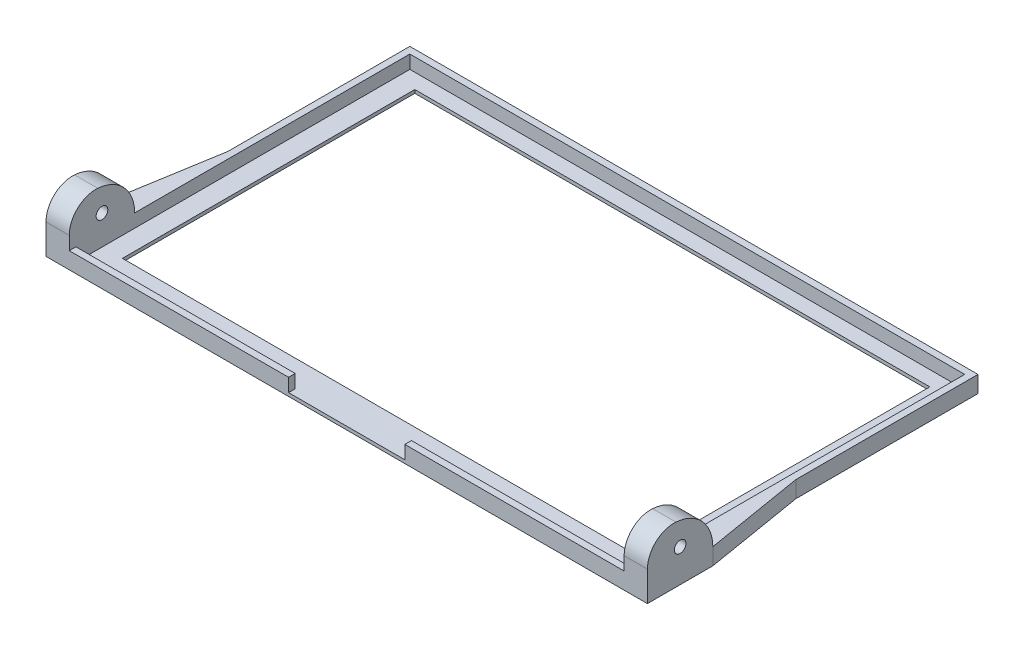
SolidWorks part; units mm, degrees
ref_plane "Front Plane" through (0, 0, 0) normal (0, 0, 1) x (1, 0, 0)
ref_plane "Top Plane" through (0, 0, 0) normal (0, 1, 0) x (1, 0, 0)
ref_plane "Right Plane" through (0, 0, 0) normal (1, 0, 0) x (0, 0, -1)
sketch "Sketch1" plane through (0, 0, 0) normal (0, 1, 0) x (1, 0, 0)
  line L0 (-85.5, 50.5) -> (85.5, 50.5)
  line L1 (-77.5, -44) -> (77.5, -44)
  line L2 (-77.5, -44) -> (-77.5, 44)
  line L3 (-77.5, 44) -> (77.5, 44)
  line L4 (77.5, -44) -> (77.5, 44)
  line L5 (-77.5, -44) -> (77.5, 44) construction
  line L6 (-77.5, 44) -> (77.5, -44) construction
  line L7 (85.5, 50.5) -> (85.5, -54)
  line L8 (85.5, -54) -> (-85.5, -54)
  line L9 (-85.5, -54) -> (-85.5, 50.5)
  point P0 (0, 0)
  dimension "D1" = 155
  dimension "D2" = 88
  dimension "D3" = 8
  dimension "D4" = 8
  dimension "D5" = 6.5
  dimension "D6" = 10
extrude "Boss-Extrude1" add sketch "Sketch1" along normal blind 1
sketch "Sketch2" plane through (0, 1, 0) normal (0, 1, 0) x (1, 0, 0)
  line L0 (-83.5, 48.5) -> (-83.5, -52)
  line L1 (-83.5, -52) -> (83.5, -52)
  line L2 (83.5, -52) -> (83.5, 48.5)
  line L3 (83.5, 48.5) -> (-83.5, 48.5)
  line L4 (-85.5, 50.5) -> (-85.5, -54)
  line L5 (-85.5, -54) -> (85.5, -54)
  line L6 (85.5, -54) -> (85.5, 50.5)
  line L7 (85.5, 50.5) -> (-85.5, 50.5)
  line L8 (-85.5, 50.5) -> (-85.5, -54)
  line L9 (-85.5, -54) -> (85.5, -54)
  line L10 (85.5, -54) -> (85.5, 50.5)
  line L11 (85.5, 50.5) -> (-85.5, 50.5)
  dimension "D1" = 0
  dimension "D2" = 2
extrude "Boss-Extrude2" add sketch "Sketch2" along normal blind 4
sketch "Sketch3" plane through (0, 1, 0) normal (0, 1, 0) x (1, 0, 0)
  line L0 (0, 0) -> (0, -52) construction
  line L1 (-83.5, -52) -> (83.5, -52) construction
  line L3 (-17.5, -56.3497) -> (17.5, -56.3497)
  line L4 (-17.5, -56.3497) -> (-17.5, -47.6503)
  line L5 (-17.5, -47.6503) -> (17.5, -47.6503)
  line L6 (17.5, -56.3497) -> (17.5, -47.6503)
  line L7 (-17.5, -56.3497) -> (17.5, -47.6503) construction
  line L8 (-17.5, -47.6503) -> (17.5, -56.3497) construction
  dimension "D1" = 35
extrude "Cut-Extrude1" cut sketch "Sketch3" along normal blind 14
sketch "Sketch4" plane through (0, 1, 0) normal (0, 1, 0) x (1, 0, 0)
  line L0 (-83.5, 48.5) -> (-83.5, -52) construction
  line L1 (-83.5, -34.3044) -> (-90.5, -34.3044)
  line L2 (-83.5, -34.3044) -> (-83.5, -54)
  line L3 (-83.5, -54) -> (-90.5, -54)
  line L4 (-90.5, -34.3044) -> (-90.5, -54)
  line L5 (-85.5, -54) -> (-17.5, -54) construction
  line L6 (0, 0) -> (0, -54) construction
  line L7 (17.5, -54) -> (-17.5, -54) construction
  line L8 (83.5, -54) -> (90.5, -54)
  line L9 (90.5, -34.3044) -> (90.5, -54)
  line L10 (83.5, -34.3044) -> (90.5, -34.3044)
  line L11 (83.5, -34.3044) -> (83.5, -54)
  dimension "D1" = 7
extrude "Boss-Extrude3" add sketch "Sketch4" along normal blind 16 and the other way blind 1
fillet "Fillet1" radius 12 2 edges at (87, 17, 34.3044) (-87, 17, 34.3044)
chamfer "Chamfer1" distance 5 distance2 30 2 edges at (85.5, 2.5, 34.3044) (-85.5, 2.5, 34.3044) first distance on face at (88, 2.5, 34.3044) first distance on face at (-88, 2.5, 34.3044)
fillet "Fillet2" radius 8 2 edges at (87, 17, 54) (-87, 17, 54)
sketch "Sketch5" plane through (-90.5, 0, 0) normal (-1, 0, 0) x (0, 0, 1)
  line L0 (44.1522, 0) -> (44.1522, 9.8927) construction
  line L1 (34.3044, 0) -> (54, 0) construction
  circle A0 centre (44.1522, 9.8927) radius 1.75
extrude "Cut-Extrude2" cut sketch "Sketch5" against normal blind 216
